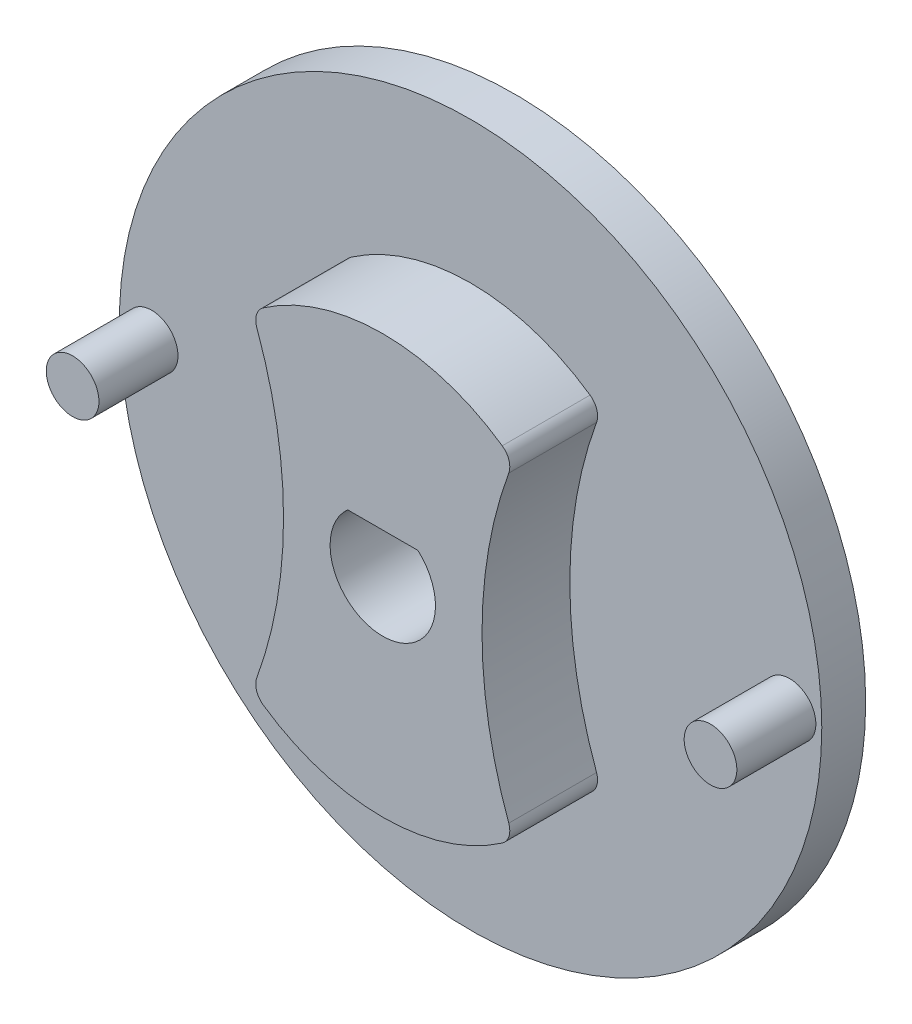
SolidWorks part; units mm, degrees
material "7075-O (SS)"
ref_plane "Front Plane" through (0, 0, 0) normal (0, 0, 1) x (1, 0, 0)
ref_plane "Top Plane" through (0, 0, 0) normal (0, 1, 0) x (1, 0, 0)
ref_plane "Right Plane" through (0, 0, 0) normal (1, 0, 0) x (0, 0, -1)
sketch "Sketch1" plane through (0, 0, 0) normal (0, 0, 1) x (1, 0, 0)
  line L0 (19.6191, 0.9484) -> (19.6191, 12.8747) construction
  circle A2 centre (19.6191, 0.9484) radius 18.1636 construction
  arc A3 (27.0554, -8.3756) -> (27.0554, 10.2725) centre (50.5208, 0.9484) cw
  arc A7 (12.1828, -8.3756) -> (12.1828, 10.2725) centre (-11.2826, 0.9484) ccw
  circle A8 centre (37.7826, 0.9484) radius 1.5 construction
  arc A10 (12.1828, -8.3756) -> (27.0554, -8.3756) centre (19.6191, 0.9484) ccw
  arc A12 (27.0554, 10.2725) -> (12.1828, 10.2725) centre (19.6191, 0.9484) ccw
  circle A22 centre (1.4555, 0.9484) radius 1.5 construction
  circle A23 centre (19.6191, 0.9484) radius 20 construction
  dimension "D1" = 36.3271
  dimension "D3" = 30.9017
  dimension "D4" = 3
  dimension "D5" = 40
  dimension "D6" = 25.25
extrude "Boss-Extrude1" add sketch "Sketch1" along normal blind 5
sketch "Sketch2" plane through (0, 0, 0) normal (0, 0, 1) x (1, 0, 0)
  circle A0 centre (19.6191, 0.9484) radius 20
  dimension "D1" = 40
extrude "Boss-Extrude2" add sketch "Sketch2" against normal blind 2.5
sketch "Sketch3" plane through (0, 0, 0) normal (0, 0, 1) x (1, 0, 0)
  circle A0 centre (1.4555, 0.9484) radius 1.5
  circle A1 centre (37.7826, 0.9484) radius 1.5
extrude "Boss-Extrude3" add sketch "Sketch3" along normal blind 4.5
sketch "Sketch4" plane through (0, 0, 0) normal (0, 0, 1) x (1, 0, 0)
  line L0 (17.6191, 3.1845) -> (21.6191, 3.1845)
  arc A0 (17.6191, 3.1845) -> (21.6191, 3.1845) centre (19.6191, 0.9484) ccw
  dimension "D1" = 6
  dimension "D2" = 4
extrude "Cut-Extrude1" cut sketch "Sketch4" against normal through all both and the other way through all
fillet "Fillet1" radius 1 4 edges at (12.1828, -8.3756, 2.5) (27.0554, -8.3756, 2.5) (27.0554, 10.2725, 2.5) (12.1828, 10.2725, 2.5)
ref_axis "Axis1" through (19.6191, 0.9484, -2.5) along (0, 0, 1)
